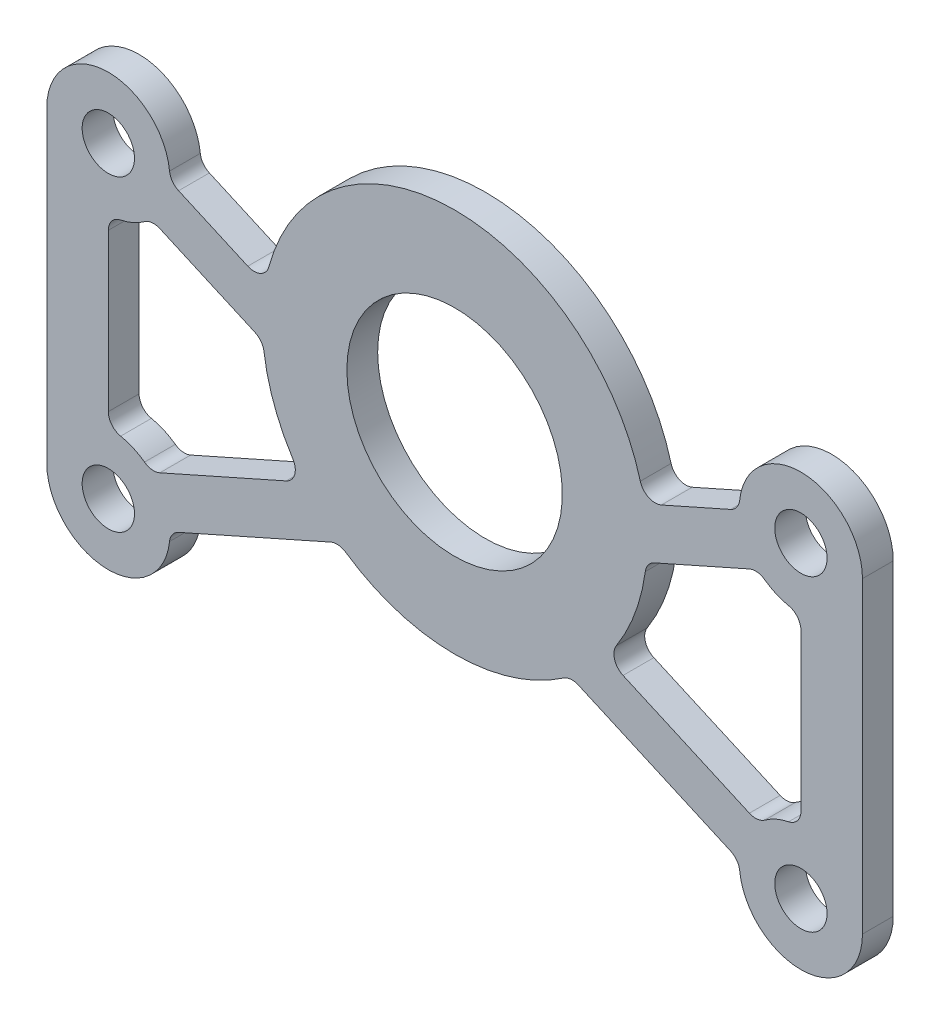
SolidWorks part; units mm, degrees
material "AR-M2"
ref_plane "正面" through (0, 0, 0) normal (0, 0, 1) x (1, 0, 0)
ref_plane "平面" through (0, 0, 0) normal (0, 1, 0) x (1, 0, 0)
ref_plane "右側面" through (0, 0, 0) normal (1, 0, 0) x (0, 0, -1)
sketch "ｽｹｯﾁ1" plane through (0, 0, 0) normal (0, 0, 1) x (1, 0, 0)
  circle A0 centre (0, 0) radius 12.5
  circle A1 centre (-22.5, 5) radius 4
  circle A2 centre (-22.5, -15) radius 4
  circle A3 centre (22.5, -15) radius 4
  circle A4 centre (22.5, 5) radius 4
  arc A5 (-26.1198, -13.2978) -> (-26.5, -15.0192) centre (-22.5, -15) ccw construction
  arc A6 (-26.3403, 6.1191) -> (-23.3, 1.0808) centre (-22.5, 5) ccw construction
  dimension "D1" = 25
extrude "ﾎﾞｽ - 押し出し1" add sketch "ｽｹｯﾁ1" along normal blind 2
sketch "ｽｹｯﾁ2" plane through (0, 0, 2) normal (0, 0, 1) x (1, 0, 0)
  line L1 (-22.5, -15) -> (-26.5, -15)
  line L2 (-22.5, -15) -> (-22.5, 5)
  line L3 (-22.5, 5) -> (-26.5, 5)
  line L4 (-26.5, -15) -> (-26.5, 5)
  line L5 (26.5, -15) -> (22.5, -15)
  line L6 (26.5, -15) -> (26.5, 5)
  line L7 (26.5, 5) -> (22.5, 5)
  line L8 (22.5, -15) -> (22.5, 5)
  circle A0 centre (-22.5, 5) radius 4 construction
  circle A1 centre (22.5, -15) radius 4 construction
  circle A3 centre (22.5, 5) radius 4 construction
  circle A4 centre (-22.5, -15) radius 4 construction
  circle A5 centre (22.5, -15) radius 4
  circle A6 centre (22.5, 5) radius 4
  circle A7 centre (-22.5, 5) radius 4
  circle A8 centre (-22.5, -15) radius 4
extrude "ﾎﾞｽ - 押し出し2" add sketch "ｽｹｯﾁ2" against normal up to surface (2 mm away) contours A8 L2 A7 L4 | A8 A5 | A6 L8 A5 L6 region at (-24.6385, -5, 2) region at (24.6385, -5, 2) up to face at (12.5, 0, 0)
sketch "ｽｹｯﾁ3" plane through (0, 0, 2) normal (0, 0, 1) x (1, 0, 0)
  line L0 (-22.5, 5) -> (22.5, -15) construction
  line L1 (-21.8908, 6.3707) -> (23.1092, -13.6293)
  line L2 (-23.1092, 3.6293) -> (21.8908, -16.3707)
  line L3 (-22.5, -15) -> (22.5, 5) construction
  line L4 (-23.1092, -13.6293) -> (21.8908, 6.3707)
  line L5 (-21.8908, -16.3707) -> (23.1092, 3.6293)
  line L6 (-17.9339, -14.6121) -> (-5.2366, -8.9688) construction
  arc A0 (-21.8908, 6.3707) -> (-23.1092, 3.6293) centre (-22.5, 5) ccw
  arc A1 (21.8908, -16.3707) -> (23.1092, -13.6293) centre (22.5, -15) ccw
  arc A2 (-23.1092, -13.6293) -> (-21.8908, -16.3707) centre (-22.5, -15) ccw
  arc A3 (23.1092, 3.6293) -> (21.8908, 6.3707) centre (22.5, 5) ccw
  circle A5 centre (0, 0) radius 12.5
  circle A6 centre (0, 0) radius 12.5
  point P4 (0, -5)
  point P9 (0, -5)
  circle M3 centre (0, 0) radius 12.5
  dimension "D1" = 0
extrude "ﾎﾞｽ - 押し出し3" add sketch "ｽｹｯﾁ3" against normal through all contours L4 A2 L5 M3 | L2 A1 L1 M3 | L1 A0 L2 M3 | L5 A3 L4 M3 region at (-18.0248, 2.9844, 2) region at (18.0248, 2.9844, 2) region at (-16.1519, -12.1986, 2) region at (16.1519, -12.1986, 2)
fillet "ﾌｨﾚｯﾄ1" radius 1 20 edges at (-18.5023, -14.8647, 1) (-7.5211, -9.9842, 1) (7.5211, -9.9842, 1) (18.5023, -14.8647, 1) (-9.8265, -7.7259, 1) (-19.7207, -12.1233, 1) (-22.5, -11, 1) (-22.5, 1, 1) (-19.7207, 2.1233, 1) (-12.4508, -1.1078, 1) (22.5, 1, 1) (22.5, -11, 1) (19.7207, -12.1233, 1) (9.8265, -7.7259, 1) (12.4508, -1.1078, 1) (19.7207, 2.1233, 1) (-12.3195, 2.1168, 1) (18.5023, 4.8647, 1) (12.3195, 2.1168, 1) (-18.5023, 4.8647, 1)
sketch "ｽｹｯﾁ5" plane through (0, 0, 0) normal (0, 0, -1) x (-1, 0, 0)
  circle A1 centre (0, 0) radius 7
  dimension "D1" = 14
extrude "ｶｯﾄ - 押し出し1" cut sketch "ｽｹｯﾁ5" against normal through all
hole_wizard "M3 すきま穴1" positions "ｽｹｯﾁ10" profile "ｽｹｯﾁ11" hole size "M3" standard "JIS" end condition through all
sketch "ｽｹｯﾁ10" plane through (0, 0, 2) normal (0, 0, 1) x (1, 0, 0)
  point P0 (-22.5, 5)
  point P3 (-22.5, -15)
  point P6 (22.5, -15)
  point P9 (22.5, 5)
sketch "ｽｹｯﾁ11" plane through (-22.5, 5, 2) normal (1, 0, 0) x (0, -1, 0)
  line L0 (0, 0) -> (0, 2)
  line L1 (0, 2) -> (1.7, 2)
  line L2 (1.7, 2) -> (1.7, 0)
  line L5 (1.7, 0) -> (0, 0)
  line L11 (0, -6.35) -> (0, 107.95) construction
  dimension "通し穴の直径" = 3.4
  dimension "通し穴の深さ" = 2
